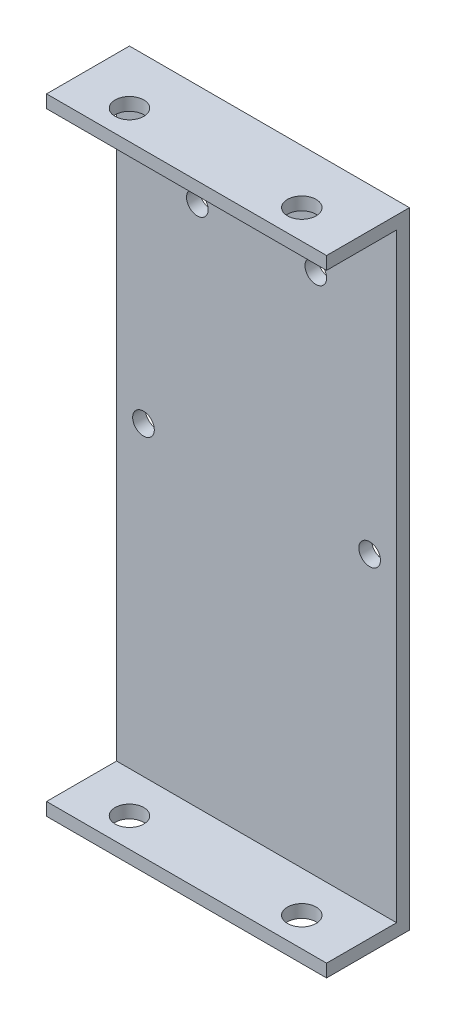
SolidWorks part; units mm, degrees
ref_plane "Front Plane" through (0, 0, 0) normal (0, 0, 1) x (1, 0, 0)
ref_plane "Top Plane" through (0, 0, 0) normal (0, 1, 0) x (1, 0, 0)
ref_plane "Right Plane" through (0, 0, 0) normal (1, 0, 0) x (0, 0, -1)
sketch "Sketch1" plane through (0, 0, 0) normal (0, 0, 1) x (1, 0, 0)
  line L0 (66.04, 81.2371) -> (66.04, 68.7911) construction
  line L1 (0, 0) -> (66.04, 0)
  line L2 (0, 0) -> (0, 147.574)
  line L3 (0, 147.574) -> (66.04, 147.574)
  line L4 (66.04, 0) -> (66.04, 147.574)
  dimension "D2" = 147.574
extrude "Boss-Extrude1" add sketch "Sketch1" along normal blind 3.0378
sketch "Sketch3" plane through (0, 0, 3.0378) normal (0, 0, 1) x (1, 0, 0)
  line L0 (66.04, 0) -> (66.04, 147.574) construction
  line L1 (0, 147.574) -> (66.04, 147.574)
  line L2 (0, 147.574) -> (0, 144.5362)
  line L3 (0, 144.5362) -> (66.04, 144.5362)
  line L4 (66.04, 147.574) -> (66.04, 144.5362)
  line L6 (0, 0) -> (66.04, 0)
  line L7 (0, 0) -> (0, 3.0378)
  line L8 (0, 3.0378) -> (66.04, 3.0378)
  line L9 (66.04, 0) -> (66.04, 3.0378)
  dimension "D1" = 3.0378
  dimension "D2" = 3.0378
extrude "Boss-Extrude2" add sketch "Sketch3" along normal blind 16.51
sketch "Sketch4" plane through (0, 0, 0) normal (0, -1, 0) x (1, 0, 0)
  line L0 (0, 19.5478) -> (66.04, 19.5478) construction
  line L3 (0, 19.5478) -> (0, 0) construction
  circle A0 centre (12.7, 12.6898) radius 3.3782
  circle A5 centre (53.34, 12.6898) radius 3.3782
  dimension "D2" = 6.7564
  dimension "D3" = 6.7564
  dimension "D4" = 6.858
  dimension "D6" = 6.858
  dimension "D1" = 40.64
  dimension "D5" = 12.7
extrude "Cut-Extrude1" cut sketch "Sketch4" against normal through all
sketch "Sketch5" plane through (0, 0, 3.0378) normal (0, 0, 1) x (1, 0, 0)
  circle A0 centre (46.99, 126.4491) radius 2.5527 construction
  circle A1 centre (19.05, 126.4491) radius 2.5527 construction
  circle A2 centre (6.35, 75.1411) radius 2.5527 construction
  circle A3 centre (59.69, 75.1411) radius 2.5527 construction
  circle A4 centre (46.99, 126.4491) radius 2.5527
  circle A5 centre (19.05, 126.4491) radius 2.5527
  circle A6 centre (6.35, 75.1411) radius 2.5527
  circle A7 centre (59.69, 75.1411) radius 2.5527
extrude "Cut-Extrude2" cut sketch "Sketch5" against normal up to surface (3.0378 mm away) up to face at (33.02, 73.787, 0)
